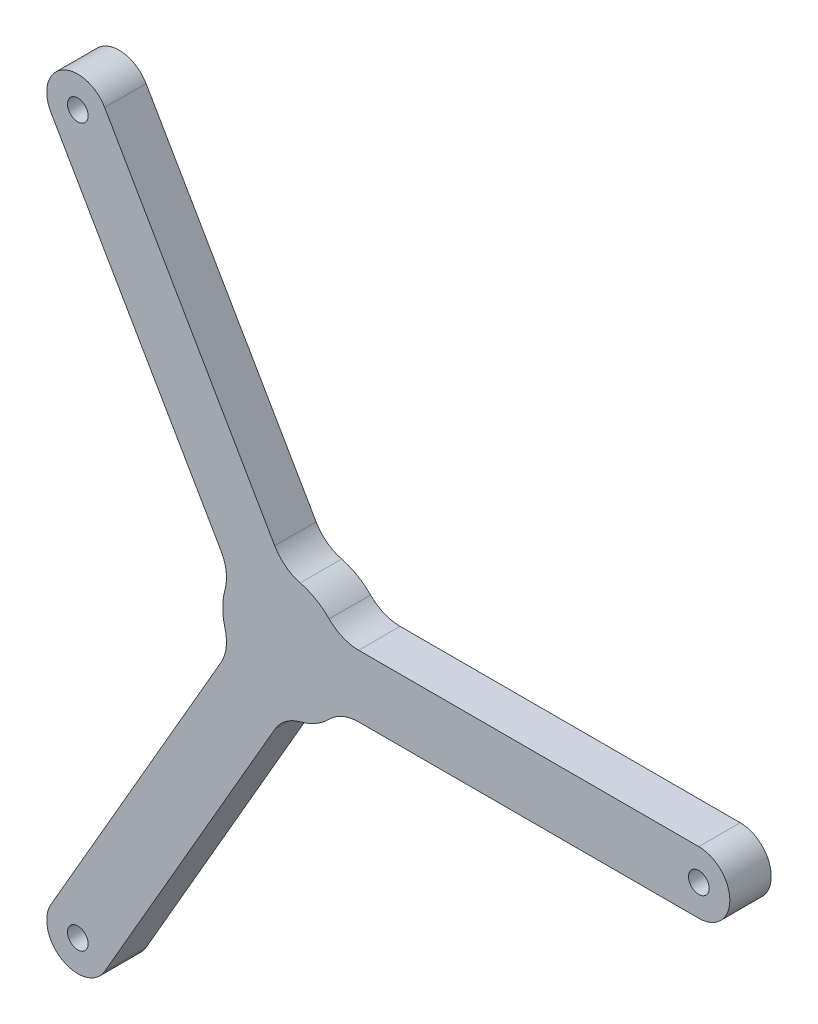
SolidWorks part; units mm, degrees
ref_plane "Front Plane" through (0, 0, 0) normal (0, 0, 1) x (1, 0, 0)
ref_plane "Top Plane" through (0, 0, 0) normal (0, 1, 0) x (1, 0, 0)
ref_plane "Right Plane" through (0, 0, 0) normal (1, 0, 0) x (0, 0, -1)
sketch "Sketch1" plane through (0, 0, 0) normal (0, 0, 1) x (1, 0, 0)
  line L0 (0, 0) -> (100, 0) construction
  line L1 (0, 7.5) -> (100, 7.5)
  line L2 (100, -7.5) -> (12.9904, -7.5)
  circle A0 centre (100, 0) radius 7.5
  circle A1 centre (0, 0) radius 15
  circle A2 centre (100, 0) radius 2.5
  point P11 (100, 0)
  dimension "pin diameter" = 5
  dimension "D1" = 15
  dimension "D2" = 30
  dimension "pin distance" = 100
extrude "Boss-Extrude1" add sketch "Sketch1" along normal blind 10 contours A1 | A1 L0 A0 L1 | L0 A1 L2 A0 | A0 A2 region at (54.2447, 3.8074, 0) region at (54.2447, -3.8074, 0) region at (14.0791, -3.7725, 0) region at (94.8467, 5.1533, 0)
fillet "Fillet1" radius 10 2 edges at (12.9904, 7.5, 5) (12.9904, -7.5, 5)
pattern_circular "CirPattern2" count 3 over 360 about axis through (0, 0, 10) along (0, 0, -1) of "Boss-Extrude1", "Fillet1"
ref_axis "Axis1" through (0, 0, 0) along (0, 0, 1)
equation "\"D1@Sketch1\"= \"pin diameter@Sketch1\" + 1"
